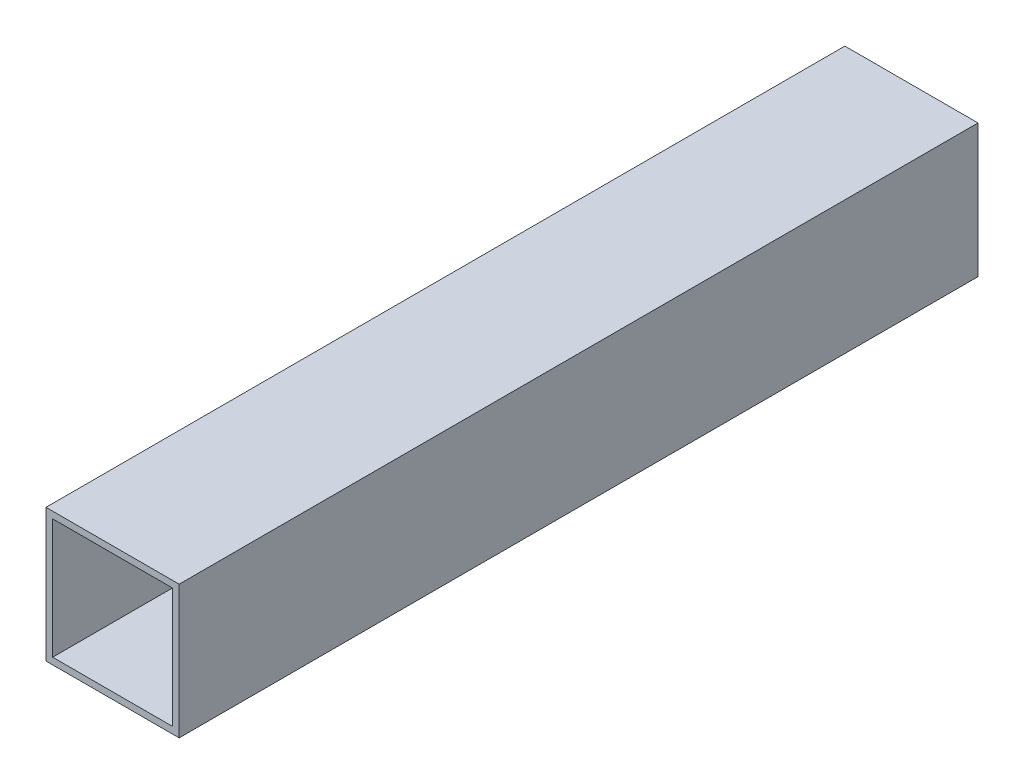
SolidWorks part; units mm, degrees
ref_plane "Plan de face" through (0, 0, 0) normal (0, 0, 1) x (1, 0, 0)
ref_plane "Plan de dessus" through (0, 0, 0) normal (0, 1, 0) x (1, 0, 0)
ref_plane "Plan de droite" through (0, 0, 0) normal (1, 0, 0) x (0, 0, -1)
sketch "Esquisse1" plane through (0, 0, 0) normal (0, 0, 1) x (1, 0, 0)
  line L0 (-450, 450) -> (450, 450)
  line L1 (-500, -500) -> (500, -500)
  line L2 (-500, -500) -> (-500, 500)
  line L3 (-500, 500) -> (500, 500)
  line L4 (500, -500) -> (500, 500)
  line L5 (-500, -500) -> (500, 500) construction
  line L6 (-500, 500) -> (500, -500) construction
  line L7 (450, -450) -> (450, 450)
  line L8 (-450, -450) -> (450, -450)
  line L9 (-450, -450) -> (-450, 450)
  point P0 (0, 0)
  dimension "D1" = 1000
  dimension "D2" = 1000
  dimension "D3" = 50
extrude "Boss.-Extru.1" add sketch "Esquisse1" along normal blind 6000
